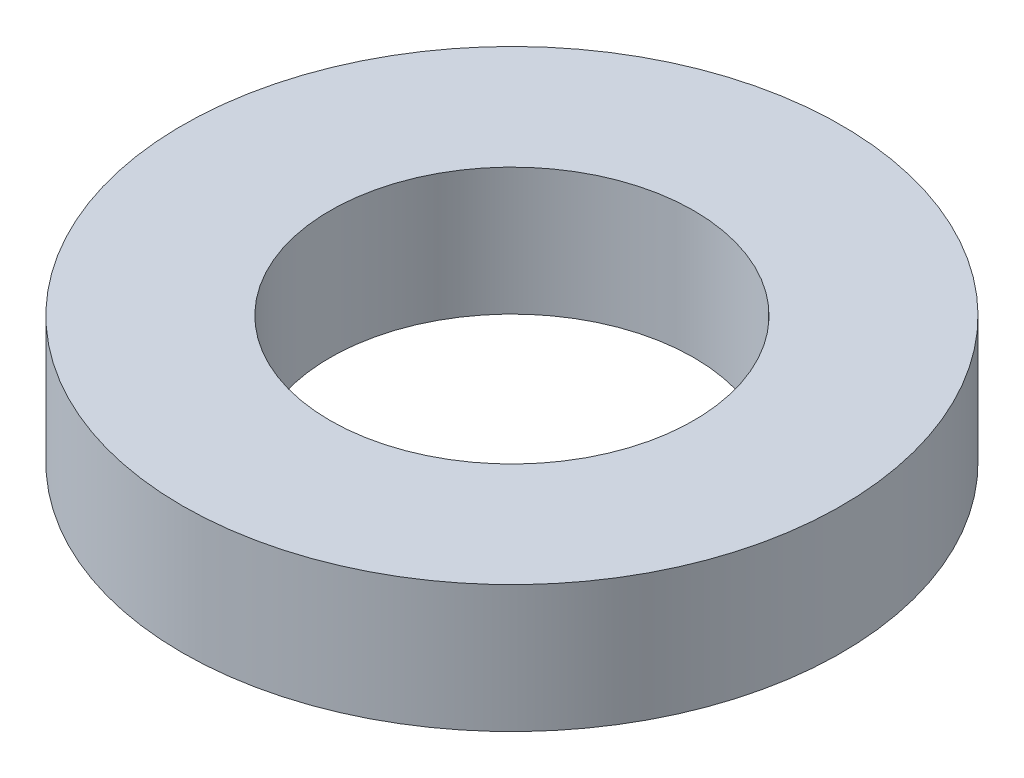
SolidWorks part; units mm, degrees
ref_plane "Front Plane" through (0, 0, 0) normal (0, 0, 1) x (1, 0, 0)
ref_plane "Top Plane" through (0, 0, 0) normal (0, 1, 0) x (1, 0, 0)
ref_plane "Right Plane" through (0, 0, 0) normal (1, 0, 0) x (0, 0, -1)
sketch "Sketch1" plane through (0, 0, 0) normal (0, 1, 0) x (1, 0, 0)
  circle A0 centre (0, 0) radius 72.5
  dimension "FLANGE_OD" = 145
extrude "Boss-Extrude1" add sketch "Sketch1" along normal blind 28
sketch "Sketch2" plane through (0, 0, 0) normal (0, 1, 0) x (1, 0, 0)
  circle A0 centre (0, 0) radius 40
  dimension "BORE_D" = 80
extrude "Cut-Extrude1" cut sketch "Sketch2" along normal through all
sketch "Sketch3" plane through (0, 28, 0) normal (0, 1, 0) x (1, 0, 0)
  circle A0 centre (0, 0) radius 25.7342 construction
  circle A1 centre (-25.7342, 0) radius 5.3982
  dimension "BOLT_D" = 10.7964
  dimension "BOLT_PCD" = 51.4685
extrude "Cut-Extrude2" cut sketch "Sketch3" against normal blind 26.5247 rebuild error yes
pattern_circular "CirPattern1" count 6 over 360 rebuild error yes
